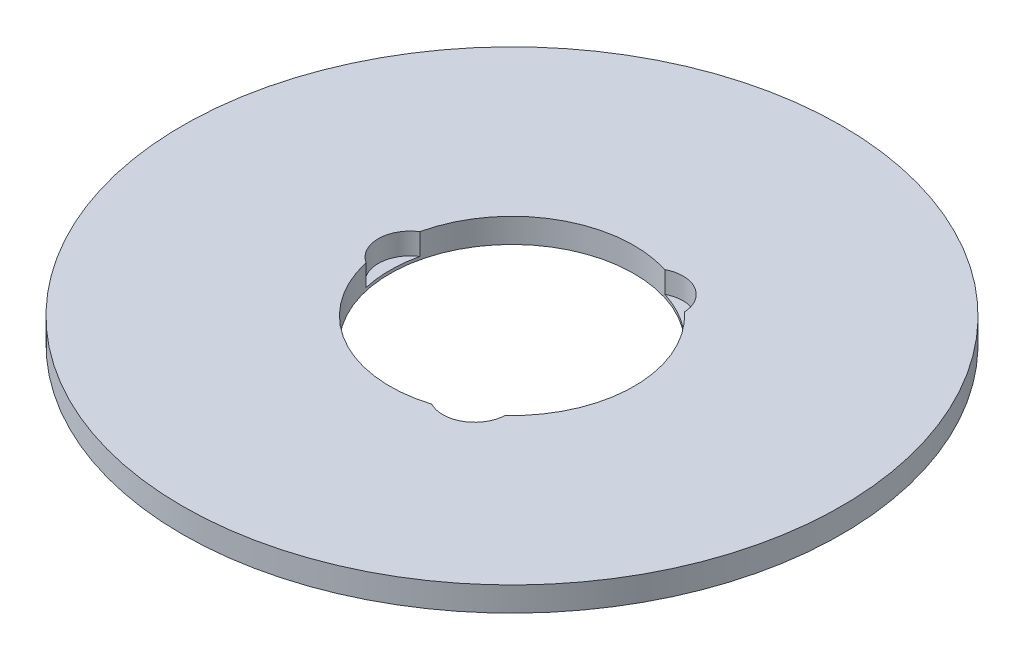
SolidWorks part; units mm, degrees
ref_plane "Front Plane" through (0, 0, 0) normal (0, 0, 1) x (1, 0, 0)
ref_plane "Top Plane" through (0, 0, 0) normal (0, 1, 0) x (1, 0, 0)
ref_plane "Right Plane" through (0, 0, 0) normal (1, 0, 0) x (0, 0, -1)
sketch "Sketch1" plane through (0, 0, 0) normal (0, 1, 0) x (1, 0, 0)
  circle A0 centre (0, 0) radius 67.5
  dimension "FLANGE_OD" = 135
extrude "Boss-Extrude1" add sketch "Sketch1" along normal blind 5
sketch "Sketch2" plane through (0, 0, 0) normal (0, 1, 0) x (1, 0, 0)
  circle A0 centre (0, 0) radius 25
  dimension "BORE_D" = 50
extrude "Cut-Extrude1" cut sketch "Sketch2" along normal through all
sketch "Sketch3" plane through (0, 5, 0) normal (0, 1, 0) x (1, 0, 0)
  circle A0 centre (0, 0) radius 20.8594 construction
  circle A1 centre (-20.8594, 0) radius 6.5363
  dimension "BOLT_D" = 13.0727
  dimension "BOLT_PCD" = 41.7188
extrude "Cut-Extrude2" cut sketch "Sketch3" against normal blind 4.4001
pattern_circular "CirPattern1" count 3 over 360 about axis through (0, 0, 0) along (0, 1, 0) of "Cut-Extrude2"
